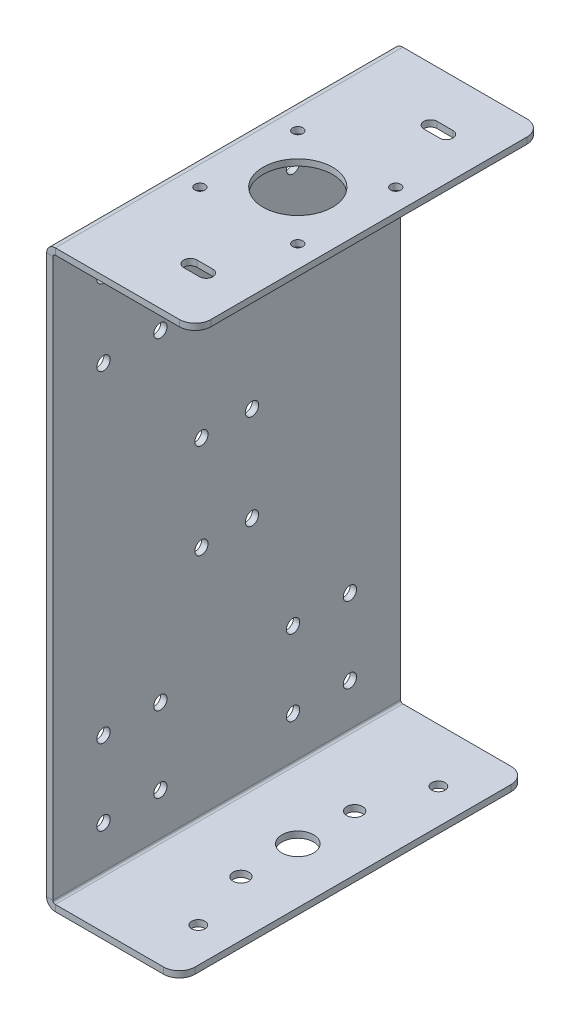
SolidWorks part; units mm, degrees
note: The reader was unsure of these and kept them because the rebuilt part matched: flange length of "Edge-Flange1", "Edge-Flange2".
ref_plane "Front Plane" through (0, 0, 0) normal (0, 0, 1) x (1, 0, 0)
ref_plane "Top Plane" through (0, 0, 0) normal (0, 1, 0) x (1, 0, 0)
ref_plane "Right Plane" through (0, 0, 0) normal (1, 0, 0) x (0, 0, -1)
sketch "Sketch1" plane through (0, 0, 0) normal (0, 0, 1) x (1, 0, 0)
  line L0 (-23.5, 91) -> (-23.5, -91)
  line L1 (55, 0) -> (-55, 0) construction
  line L2 (0, -55) -> (0, 55) construction
  dimension "D1" = 182
  dimension "D2" = 91
  dimension "D3" = 23.5
base flange "Base-Flange1" sketch "Sketch1" end condition mid plane depth 110 reverse direction no thickness 2 reverse thickness direction yes bend radius 0.7366
edge flange "Edge-Flange1" sketch "Sketch8" flange angle 90 flange length 47 flange position material inside bend radius 0.7366 thickness 2 relief rectangular parameters "D6"=10
sketch "Sketch8" plane through (-21.5, 91, 0) normal (0, -1, 0) x (0, 0, -1)
  line L2 (-55, 0) -> (-55, 45)
  line L3 (-55, 45) -> (55, 45)
  line L4 (55, 45) -> (55, 0)
  line L5 (55, 0) -> (-55, 0) construction
  line L6 (55, 0) -> (-55, 0)
bend "EdgeBend1" bend radius 0.7366 bend angle 90 parameters "D5"=1
edge flange "Edge-Flange2" sketch "Sketch11" flange angle 90 flange length 42 flange position material inside bend radius 0.7366 thickness 2 relief rectangular parameters "D6"=10
sketch "Sketch11" plane through (-21.5, -91, 0) normal (0, 1, 0) x (0, 0, 1)
  line L2 (-55, 0) -> (-55, 40)
  line L3 (-55, 40) -> (55, 40)
  line L4 (55, 40) -> (55, 0)
  line L5 (55, 0) -> (-55, 0) construction
  line L6 (55, 0) -> (-55, 0)
bend "EdgeBend2" bend radius 0.7366 bend angle 90 parameters "D5"=2
fillet "Fillet1" radius 5 4 edges at (23.5, 90, -55) (23.5, 90, 55) (18.5, -90, -55) (18.5, -90, 55)
sketch "Sketch13" plane through (-23.5, 0, 0) normal (-1, 0, 0) x (0, 0, 1)
  circle A0 centre (-39, 75) radius 2.1
  circle A1 centre (-39, 51) radius 2.1
  circle A2 centre (-21, 75) radius 2.1
  circle A3 centre (-21, 51) radius 2.1
  circle A4 centre (21, 75) radius 2.1
  circle A5 centre (21, 51) radius 2.1
  circle A6 centre (39, 75) radius 2.1
  circle A7 centre (39, 51) radius 2.1
extrude "Cut-Extrude1" cut sketch "Sketch13" against normal up to next normal cut yes
mirror "Mirror1" about plane through (0, 0, 0) normal (0, 1, 0) of "Cut-Extrude1"
sketch "Sketch14" plane through (0, 91, 0) normal (0, 1, 0) x (1, 0, 0)
  circle A0 centre (1, 0) radius 11
  circle A1 centre (-14.5, 15.5) radius 1.6
  circle A2 centre (16.5, 15.5) radius 1.6
  circle A3 centre (-14.5, -15.5) radius 1.6
  circle A4 centre (16.5, -15.5) radius 1.6
extrude "Cut-Extrude2" cut sketch "Sketch14" against normal up to next normal cut yes
sketch "Sketch15" plane through (0, -91, 0) normal (0, -1, 0) x (1, 0, 0)
  circle A0 centre (1, 18) radius 2.5
  circle A1 centre (1, -18) radius 2.5
  circle A2 centre (1, 0) radius 5
extrude "Cut-Extrude3" cut sketch "Sketch15" against normal up to next normal cut yes
sketch "Sketch16" plane through (-23.5, 0, 0) normal (-1, 0, 0) x (0, 0, 1)
  circle A0 centre (-8, 15) radius 2.1
  circle A1 centre (-8, -15) radius 2.1
  circle A2 centre (8, 15) radius 2.1
  circle A3 centre (8, -15) radius 2.1
extrude "Cut-Extrude4" cut sketch "Sketch16" against normal up to next normal cut yes
sketch "Sketch17" plane through (0, 91, 0) normal (0, 1, 0) x (1, 0, 0)
  line L8 (5, 40.1) -> (10, 40.1)
  line L9 (5, 35.9) -> (10, 35.9)
  line L10 (5, -35.9) -> (10, -35.9)
  line L11 (5, -40.1) -> (10, -40.1)
  arc A2 (10, 35.9) -> (10, 40.1) centre (10, 38) ccw
  arc A3 (5, 40.1) -> (5, 35.9) centre (5, 38) ccw
  arc A4 (10, -40.1) -> (10, -35.9) centre (10, -38) ccw
  arc A5 (5, -35.9) -> (5, -40.1) centre (5, -38) ccw
extrude "Cut-Extrude5" cut sketch "Sketch17" against normal up to next normal cut yes
sketch "Sketch18" plane through (0, -91, 0) normal (0, -1, 0) x (1, 0, 0)
  line L0 (-23.5, -55) -> (-23.5, 55) construction
  circle A0 centre (7.5, 38) radius 2.1
  circle A1 centre (7.5, -38) radius 2.1
  dimension "D1" = 31
  dimension "D2" = 31
extrude "Cut-Extrude6" cut sketch "Sketch18" against normal up to next normal cut yes
sketch "Bend-Lines1" [suppressed] plane through (0, 0, 0) normal (0, 1, 0) x (1, 0, 0)
sketch "Bounding-Box1" [suppressed] plane through (0, 0, 0) normal (0, 1, 0) x (1, 0, 0)
sheet metal parameters "Sheet-Metal1" thickness 2 parameters "D1"=0.7366
flat pattern "Flat-Pattern1" [suppressed]
sketch "Bend-Lines2" plane through (0, 0, 0) normal (0, 1, 0) x (1, 0, 0)
sketch3d "Bounding-Box2" [suppressed]
  line L0 (110, -182, 0) -> (110, 0, 0) construction
  line L1 (0, -182, 0) -> (0, 0, 0) construction
  line L2 (110, -182, 0) -> (0, -182, 0) construction
  line L3 (110, 0, 0) -> (0, 0, 0) construction
sheet metal parameters "Sheet-Metal2" thickness 2 parameters "D1"=0.7366
flat pattern "Flat-Pattern1"
sketch "Bend-Lines2" plane through (-21.5, 0, 0) normal (1, 0, 0) x (0, 0, -1)
  line L0 (-55, 89.6273) -> (55, 89.6273) construction
  line L1 (-55, 89.6273) -> (55, 89.6273) construction
sketch3d "Bounding-Box2" [suppressed]
  line L0 (110, -182, 0) -> (110, 44.2546, 0) construction
  line L1 (0, -182, 0) -> (0, 44.2546, 0) construction
  line L2 (110, -182, 0) -> (0, -182, 0) construction
  line L3 (110, 44.2546, 0) -> (0, 44.2546, 0) construction
bend of the flat pattern "Flatten-<EdgeBend1>1"
sheet metal parameters "Sheet-Metal3" thickness 2 parameters "D1"=0.7366
flat pattern "Flat-Pattern1"
sketch "Bend-Lines2" plane through (-21.5, 0, 0) normal (1, 0, 0) x (0, 0, -1)
  line L0 (-55, 89.6273) -> (55, 89.6273) construction
  line L1 (-55, 89.6273) -> (55, 89.6273) construction
  line L2 (55, -89.6273) -> (-55, -89.6273) construction
  line L3 (55, -89.6273) -> (-55, -89.6273) construction
sketch3d "Bounding-Box2" [suppressed]
  line L0 (0, -221.2546, 0) -> (0, 44.2546, 0) construction
  line L1 (110, -221.2546, 0) -> (110, 44.2546, 0) construction
  line L2 (0, -221.2546, 0) -> (110, -221.2546, 0) construction
  line L3 (0, 44.2546, 0) -> (110, 44.2546, 0) construction
bend of the flat pattern "Flatten-<EdgeBend1>1"
bend of the flat pattern "Flatten-<EdgeBend2>1"
sheet metal parameters "Sheet-Metal4" thickness 2 parameters "D1"=0.7366
flat pattern "Flat-Pattern1"
sketch "Bend-Lines2" plane through (-21.5, 0, 0) normal (1, 0, 0) x (0, 0, -1)
  line L0 (-55, 89.6273) -> (55, 89.6273) construction
  line L1 (-55, 89.6273) -> (55, 89.6273) construction
  line L2 (55, -89.6273) -> (-55, -89.6273) construction
  line L3 (55, -89.6273) -> (-55, -89.6273) construction
sketch3d "Bounding-Box2" [suppressed]
  line L0 (0, -221.2546, 0) -> (0, 44.2546, 0) construction
  line L1 (110, -221.2546, 0) -> (110, 44.2546, 0) construction
  line L2 (0, -221.2546, 0) -> (110, -221.2546, 0) construction
  line L3 (0, 44.2546, 0) -> (110, 44.2546, 0) construction
bend of the flat pattern "Flatten-<EdgeBend1>1"
bend of the flat pattern "Flatten-<EdgeBend2>1"
sheet metal parameters "Sheet-Metal5" thickness 2 parameters "D1"=0.7366
flat pattern "Flat-Pattern1"
sketch "Bend-Lines2" plane through (-21.5, 0, 0) normal (1, 0, 0) x (0, 0, -1)
  line L0 (-55, 89.6273) -> (55, 89.6273) construction
  line L1 (-55, 89.6273) -> (55, 89.6273) construction
  line L2 (55, -89.6273) -> (-55, -89.6273) construction
  line L3 (55, -89.6273) -> (-55, -89.6273) construction
sketch3d "Bounding-Box2" [suppressed]
  line L0 (0, -221.2546, 0) -> (0, 44.2546, 0) construction
  line L1 (110, -221.2546, 0) -> (110, 44.2546, 0) construction
  line L2 (0, -221.2546, 0) -> (110, -221.2546, 0) construction
  line L3 (0, 44.2546, 0) -> (110, 44.2546, 0) construction
bend of the flat pattern "Flatten-<EdgeBend1>1"
bend of the flat pattern "Flatten-<EdgeBend2>1"
sheet metal parameters "Sheet-Metal6" thickness 2 parameters "D1"=0.7366
flat pattern "Flat-Pattern1"
sketch "Bend-Lines2" plane through (-21.5, 0, 0) normal (1, 0, 0) x (0, 0, -1)
  line L0 (-55, 89.6273) -> (55, 89.6273) construction
  line L1 (-55, 89.6273) -> (55, 89.6273) construction
  line L2 (55, -89.6273) -> (-55, -89.6273) construction
  line L3 (55, -89.6273) -> (-55, -89.6273) construction
sketch3d "Bounding-Box2" [suppressed]
  line L0 (0, -221.2546, 0) -> (0, 44.2546, 0) construction
  line L1 (110, -221.2546, 0) -> (110, 44.2546, 0) construction
  line L2 (0, -221.2546, 0) -> (110, -221.2546, 0) construction
  line L3 (0, 44.2546, 0) -> (110, 44.2546, 0) construction
bend of the flat pattern "Flatten-<EdgeBend1>1"
bend of the flat pattern "Flatten-<EdgeBend2>1"
sheet metal parameters "Sheet-Metal7" thickness 2 parameters "D1"=0.7366
flat pattern "Flat-Pattern1"
sketch "Bend-Lines2" plane through (-21.5, 0, 0) normal (1, 0, 0) x (0, 0, -1)
  line L0 (-55, 89.6273) -> (55, 89.6273) construction
  line L1 (-55, 89.6273) -> (55, 89.6273) construction
  line L2 (55, -89.6273) -> (-55, -89.6273) construction
  line L3 (55, -89.6273) -> (-55, -89.6273) construction
sketch3d "Bounding-Box2" [suppressed]
  line L0 (0, -221.2546, 0) -> (0, 44.2546, 0) construction
  line L1 (110, -221.2546, 0) -> (110, 44.2546, 0) construction
  line L2 (0, -221.2546, 0) -> (110, -221.2546, 0) construction
  line L3 (0, 44.2546, 0) -> (110, 44.2546, 0) construction
bend of the flat pattern "Flatten-<EdgeBend1>1"
bend of the flat pattern "Flatten-<EdgeBend2>1"
sheet metal parameters "Sheet-Metal8" thickness 2 parameters "D1"=0.7366
flat pattern "Flat-Pattern1"
sketch "Bend-Lines2" plane through (-21.5, 0, 0) normal (1, 0, 0) x (0, 0, -1)
  line L0 (-55, 89.6273) -> (55, 89.6273) construction
  line L1 (-55, 89.6273) -> (55, 89.6273) construction
  line L2 (55, -89.6273) -> (-55, -89.6273) construction
  line L3 (55, -89.6273) -> (-55, -89.6273) construction
sketch3d "Bounding-Box2" [suppressed]
  line L0 (0, -221.2546, 0) -> (0, 44.2546, 0) construction
  line L1 (110, -221.2546, 0) -> (110, 44.2546, 0) construction
  line L2 (0, -221.2546, 0) -> (110, -221.2546, 0) construction
  line L3 (0, 44.2546, 0) -> (110, 44.2546, 0) construction
bend of the flat pattern "Flatten-<EdgeBend1>1"
bend of the flat pattern "Flatten-<EdgeBend2>1"
sheet metal parameters "Sheet-Metal9" thickness 2 parameters "D1"=0.7366
flat pattern "Flat-Pattern1"
sketch "Bend-Lines2" plane through (-21.5, 0, 0) normal (1, 0, 0) x (0, 0, -1)
  line L0 (-55, 89.6273) -> (55, 89.6273) construction
  line L1 (-55, 89.6273) -> (55, 89.6273) construction
  line L2 (55, -89.6273) -> (-55, -89.6273) construction
  line L3 (55, -89.6273) -> (-55, -89.6273) construction
sketch3d "Bounding-Box2" [suppressed]
  line L0 (0, -221.2546, 0) -> (0, 44.2546, 0) construction
  line L1 (110, -221.2546, 0) -> (110, 44.2546, 0) construction
  line L2 (0, -221.2546, 0) -> (110, -221.2546, 0) construction
  line L3 (0, 44.2546, 0) -> (110, 44.2546, 0) construction
bend of the flat pattern "Flatten-<EdgeBend1>1"
bend of the flat pattern "Flatten-<EdgeBend2>1"
sheet metal parameters "Sheet-Metal10" thickness 2 parameters "D1"=0.7366
flat pattern "Flat-Pattern1"
sketch "Bend-Lines2" plane through (-21.5, 0, 0) normal (1, 0, 0) x (0, 0, -1)
  line L0 (-55, 89.6273) -> (55, 89.6273) construction
  line L1 (-55, 89.6273) -> (55, 89.6273) construction
  line L2 (55, -89.6273) -> (-55, -89.6273) construction
  line L3 (55, -89.6273) -> (-55, -89.6273) construction
sketch3d "Bounding-Box2" [suppressed]
  line L0 (0, -221.2546, 0) -> (0, 44.2546, 0) construction
  line L1 (110, -221.2546, 0) -> (110, 44.2546, 0) construction
  line L2 (0, -221.2546, 0) -> (110, -221.2546, 0) construction
  line L3 (0, 44.2546, 0) -> (110, 44.2546, 0) construction
bend of the flat pattern "Flatten-<EdgeBend1>1"
bend of the flat pattern "Flatten-<EdgeBend2>1"
